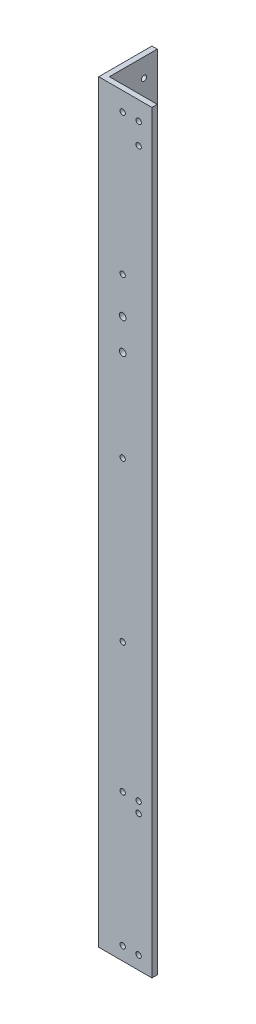
SolidWorks part; units mm, degrees
ref_plane "Front Plane" through (0, 0, 0) normal (0, 0, 1) x (1, 0, 0)
ref_plane "Top Plane" through (0, 0, 0) normal (0, 1, 0) x (1, 0, 0)
ref_plane "Right Plane" through (0, 0, 0) normal (1, 0, 0) x (0, 0, -1)
sketch "Sketch2" plane through (0, 0, 0) normal (0, 1, 0) x (1, 0, 0)
  line L0 (0, 31.75) -> (3.175, 31.75)
  line L1 (3.175, 31.75) -> (3.175, 3.175)
  line L2 (3.175, 3.175) -> (31.75, 3.175)
  line L3 (31.75, 3.175) -> (31.75, 0)
  line L4 (31.75, 0) -> (0, 0)
  line L5 (0, 0) -> (0, 31.75)
  point P9 (1.5875, 31.75)
  point P10 (31.75, 1.5875)
  dimension "D4" = 3.175
  dimension "D1" = 31.75
  dimension "D2" = 31.75
  dimension "D3" = 3.175
extrude "Boss-Extrude1" add sketch "Sketch2" along normal blind 450
sketch "FrontSideHoles-Sketch3" plane through (0, 0, 0) normal (0, 0, 1) x (1, 0, 0)
  line L0 (0, 0) -> (31.75, 0) construction
  line L1 (0, 450) -> (0, 0) construction
  circle A1 centre (23.8125, 81.1125) radius 1.5875
  circle A2 centre (14.2875, 87.4625) radius 1.5875
  circle A3 centre (23.8125, 87.4625) radius 1.5875
  circle A4 centre (14.2875, 438.8875) radius 1.5875
  circle A6 centre (23.8125, 438.8875) radius 1.5875
  circle A7 centre (23.8125, 426.1875) radius 1.5875
  circle A8 centre (14.2875, 333.1776) radius 2
  circle A9 centre (14.2875, 314.6526) radius 2
  circle A10 centre (14.2875, 260) radius 1.5875
  circle A11 centre (14.2875, 165) radius 1.5875
  circle A12 centre (14.2875, 355) radius 1.5875
  circle A13 centre (14.2875, 7.9375) radius 1.5875
  circle A14 centre (23.8125, 7.9375) radius 1.5875
  dimension "D4" = 3.175
  dimension "D15" = 4
  dimension "D8" = 11.1125
  dimension "D11" = 18.525
  dimension "D9" = 314.6526
  dimension "D6" = 165
  dimension "D10" = 95
  dimension "D13" = 95
  dimension "D12" = 7.9375
  dimension "D3" = 9.525
  dimension "D2" = 14.2875
  dimension "D5" = 6.35
  dimension "D14" = 81.1125
  dimension "D7" = 12.7
sketch "LeftSideHoles-Sketch4" plane through (0, 0, 0) normal (-1, 0, 0) x (0, 0, 1)
  line L0 (-31.75, 450) -> (0, 450) construction
  line L1 (0, 450) -> (0, 0) construction
  line L3 (-31.75, 0) -> (0, 0) construction
  circle A0 centre (-23.8125, 81.1125) radius 1.5875
  circle A1 centre (-14.2875, 81.1125) radius 1.5875
  circle A2 centre (-23.8125, 87.4625) radius 1.5875
  circle A4 centre (-23.8125, 438.8875) radius 1.5875
  circle A6 centre (-23.8125, 426.1875) radius 1.5875
  circle A7 centre (-14.2875, 426.1875) radius 1.5875
  circle A8 centre (-23.8125, 327.6026) radius 1.5875
  circle A9 centre (-14.2875, 327.6026) radius 1.5875
  circle A10 centre (-23.8125, 292.6776) radius 1.5875
  circle A11 centre (-14.2875, 292.6776) radius 1.5875
  circle A12 centre (-23.8125, 7.9375) radius 1.5875
  circle A13 centre (-14.2875, 7.9375) radius 1.5875
  circle A14 centre (-14.2875, 165) radius 1.5875
  circle A15 centre (-14.2875, 260) radius 1.5875
  circle A16 centre (-14.2875, 355) radius 1.5875
  dimension "D4" = 3.175
  dimension "D13" = 95
  dimension "D2" = 14.2875
  dimension "D5" = 6.35
  dimension "D7" = 12.7
  dimension "D3" = 81.1125
  dimension "D6" = 11.1125
  dimension "D10" = 7.9375
  dimension "D9" = 34.925
  dimension "D11" = 9.525
  dimension "D8" = 327.6026
  dimension "D12" = 165
  dimension "D14" = 95
extrude "FrontSideHoles-Cut-Extrude1" cut sketch "FrontSideHoles-Sketch3" against normal blind 3.175
extrude "LeftSideHoles-Cut-Extrude2" cut sketch "LeftSideHoles-Sketch4" against normal blind 3.175
equation "\"RailThickness\"= .125in'Spec"
equation "\"VSWidth\"= 1.25in'Spec"
equation "\"VSHeight\"= 1.25in'Spec"
equation "\"VSLength\"= 450mm"
equation "\"HoleOffsetFromEdge\"= \"RailThickness\" * 2.5"
equation "\"HoleOffsetFromSide\"= \"RailThickness\" * 3.5"
equation "\"LegHeight\"= 70mm'Space needed for PSU/Stepper/Electronics"
equation "\"VSBottomSideRailHoleY1FromBottomOfLowerRail\"= \"V1 BottomOfLowerRail\" + \"HoleOffsetFromSide\"'Equals 70.1125"
equation "\"VSSideRailHoleX1FromSide\"= \"HoleOffsetFromSide\" + \"RailThickness\""
equation "\"FasteningHoleDiameter\"= .125in"
equation "\"VSBottomSideRailHoleY2FromY1\"= \"LowerRailHeight\" - \"HoleOffsetFromSide\" - \"HoleOffsetFromEdge\"'Equals 6.35"
equation "\"VSTopSideRailHoleY1FromEdge\"= \"HoleOffsetFromEdge\" + \"RailThickness\""
equation "\"D4@FrontSideHoles-Sketch3\" = \"FasteningHoleDiameter\""
equation "\"D1@Boss-Extrude1\"=\"VSLength\""
equation "\"D4@LeftSideHoles-Sketch4\" = \"FasteningHoleDiameter\""
equation "\"D3@LeftSideHoles-Sketch4\"= \"VSBottomSideRailHoleY1FromBottomOfLowerRail\""
equation "\"D8@FrontSideHoles-Sketch3\" = \"VSTopSideRailHoleY1FromEdge\""
equation "\"D6@LeftSideHoles-Sketch4\" = \"VSTopSideRailHoleY1FromEdge\""
equation "\"VSMidSideRailHoleY1FromV8TopOfMidSideRail\"= \"V8 ToTopOfMidSideRail\" - \"HoleOffsetFromEdge\"'Equals 308.2875"
equation "\"LowerRailHeight\"= 1.00in"
equation "\"D1@Sketch2\"=\"VSHeight\""
equation "\"D2@Sketch2\"=\"VSWidth\""
equation "\"TopRailHeight\"= 1.25in"
equation "\"MidLeftOrRightSideRailHeight\"= 2.0in"
equation "\"D10@LeftSideHoles-Sketch4\"=\"HoleOffsetFromEdge\""
equation "\"VSMidSideRailHoleY2FromY1\"= \"MidLeftOrRightSideRailHeight\" - \"HoleOffsetFromEdge\" * 2'Equals 34.925"
equation "\"D9@LeftSideHoles-Sketch4\"=\"VSMidSideRailHoleY2FromY1\""
equation "\"VSSideRailHoleX2FromX1\"= \"VSWidth\" - \"VSSideRailHoleX1FromSide\" - \"HoleOffsetFromEdge\""
equation "\"D11@LeftSideHoles-Sketch4\"=\"VSSideRailHoleX2FromX1\""
equation "\"VSTopSideRailHoleY2FromY1\"= \"TopRailHeight\" - \"VSTopSideRailHoleY1FromEdge\" - \"HoleOffsetFromEdge\"'Equals 12.7"
equation "\"D7@LeftSideHoles-Sketch4\"=\"VSTopSideRailHoleY2FromY1\""
equation "\"BeltTensionerInnerHeight\"= \"20TGT2PulleyWidth\" * 2 + \"1mmSpacer\" * 3"
equation "\"20TGT2PulleyWidth\"= 8.7mm'The STL of the Pulley in the diagram is a bit larger"
equation "\"1mmSpacer\"= 1mm"
equation "\"BeltTensionerHeight\"= \"BeltTensionerInnerHeight\" + \"BeltTensionerUpperLowerWallThickness\" * 2"
equation "\"BeltTensionerUpperLowerWallThickness\"= 7mm"
equation "\"D11@FrontSideHoles-Sketch3\"=\"VSBeltTensionerHoleY2FromY1\""
equation "\"VSBeltTensionerHoleY1FromBottom\"= \"V9 FromBottomGantryPulleyToBottomOfBeltTensioner\" + \"HoleOffsetFromEdge\""
equation "\"VSBeltTensionerHoleY2FromY1\"= \"BeltTensionerHeight\" - \"HoleOffsetFromEdge\" * 2"
equation "\"V1 BottomOfLowerRail\"= \"LegHeight\""
equation "\"StepperShaftLength\"= 24mm'Pulley will be attached to the end"
equation "\"ZAxisLeadScrewLength\"= 200mm"
equation "\"LM8UUHeight\"= 24mm'Spec"
equation "\"V2 ToBedAtTopOfZAxis\"= \"V1 BottomOfLowerRail\" - \"LowerEnclosureThickness\" + \"StepperShaftLength\" + \"ZAxisLeadScrewLength\" - \"LM8UUHeight\" / 2"
equation "\"HotEndToTopOfXAxisGB\"= 63.315144mm'Measured from the100.Should be 63.315144"
equation "\"TopOfGBToBottomOfLinearRail\"= \"LinearGBWidth\" / 2 + \"LinearRailWidth\" / 2"
equation "\"LinearGBWidth\"= 27mm'Spec"
equation "\"V5 ToBottomOfXAxisLinearRail\"= \"V4 ToTopOfBuildPlate/HotEndTip\" + \"HotEndToTopOfXAxisGB\" - \"TopOfGBToBottomOfLinearRail\""
equation "\"LinearRailWidth\"= 12mm'Spec"
equation "\"V6 ToBottomOfGantryPulley\"= \"V5 ToBottomOfXAxisLinearRail\" - \"DistanceFromGABTopToLowerPulley\""
equation "\"GABUpperHeight\"= 6mm"
equation "\"GABMidWallHeight\"= 28mm'Must equal 28 or changes alignment"
equation "\"GABMidShortRiserHeight\"= \"GABMidWallHeight\" / 2 - \"20TGT2PulleyWidth\"'Equals 5.3"
equation "\"GABRiserBossOffset\"= 0.8mm'Aligns Pulleys"
equation "\"DistanceFromGABTopToLowerPulley\"= \"GABUpperHeight\" + \"GABMidWallHeight\" - \"GABMidShortRiserHeight\" + \"GABRiserBossOffset\" / 2"
equation "\"V7 ToTopOfMidBackRail\"= \"V6 ToBottomOfGantryPulley\" + \"StepperShaftLength\""
equation "\"D8@LeftSideHoles-Sketch4\"= \"VSMidSideRailHoleY1FromV8TopOfMidSideRail\""
equation "\"BedToBuildPlateStandoffLength\"= 15mm"
equation "\"BuildPlateHeight\"= 8mm'Spec"
equation "\"V4 ToTopOfBuildPlate/HotEndTip\"= \"V2 ToBedAtTopOfZAxis\" + \"BedToBuildPlateStandoffLength\" + \"BuildPlateHeight\""
equation "\"D9@FrontSideHoles-Sketch3\"=\"VSBeltTensionerHoleY1FromBottom\""
equation "\"V8 ToTopOfMidSideRail\"= \"V7 ToTopOfMidBackRail\" - \"RailThickness\""
equation "\"V9 FromBottomGantryPulleyToBottomOfBeltTensioner\"= \"V6 ToBottomOfGantryPulley\" - \"BeltTensionerUpperLowerWallThickness\" - \"1mmSpacer\""
equation "\"BeltTensionerMountingHoleOffsetFromEdge\"= \"HoleOffsetFromEdge\""
equation "\"VSBeltTensionerXMountingHoleOffsetFromSide\"= \"BeltTensionerMountingHoleOffsetFromEdge\" + \"RailThickness\" * 2"
equation "\"VSEnclosureOffsets\"= ( \"VSLength\" - \"LegHeight\" ) / 4"
equation "\"D6@FrontSideHoles-Sketch3\"=\"LegHeight\" + \"VSEnclosureOffsets\""
equation "\"D10@FrontSideHoles-Sketch3\"=\"VSEnclosureOffsets\""
equation "\"D13@FrontSideHoles-Sketch3\"=\"VSEnclosureOffsets\""
equation "\"D12@FrontSideHoles-Sketch3\"=\"HoleOffsetFromEdge\""
equation "\"D13@LeftSideHoles-Sketch4\"=\"VSEnclosureOffsets\""
equation "\"D14@LeftSideHoles-Sketch4\"=\"VSEnclosureOffsets\""
equation "\"D12@LeftSideHoles-Sketch4\"=\"LegHeight\" + \"VSEnclosureOffsets\""
equation "\"D3@FrontSideHoles-Sketch3\"=\"VSSideRailHoleX2FromX1\""
equation "\"D2@FrontSideHoles-Sketch3\"=\"VSSideRailHoleX1FromSide\""
equation "\"D5@FrontSideHoles-Sketch3\"=\"VSBottomSideRailHoleY2FromY1\""
equation "\"D14@FrontSideHoles-Sketch3\"=\"VSBottomSideRailHoleY1FromBottomOfLowerRail\""
equation "\"D7@FrontSideHoles-Sketch3\"=\"VSTopSideRailHoleY2FromY1\""
equation "\"D5@LeftSideHoles-Sketch4\"=\"VSBottomSideRailHoleY2FromY1\""
equation "\"BeltTensionerMountingHoleDiameter\"= 4.0mm"
equation "\"D15@FrontSideHoles-Sketch3\"=\"BeltTensionerMountingHoleDiameter\""
equation "\"LowerEnclosureThickness\"= 5mm"
